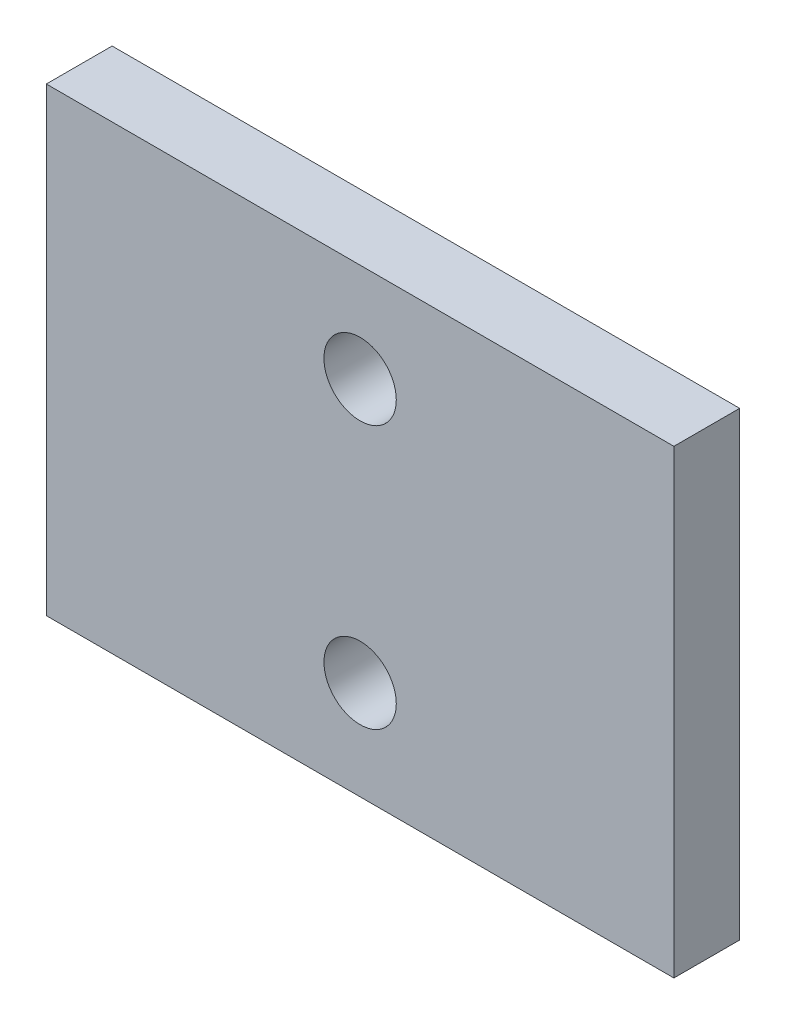
SolidWorks part; units mm, degrees
ref_plane "Front Plane" through (0, 0, 0) normal (0, 0, 1) x (1, 0, 0)
ref_plane "Top Plane" through (0, 0, 0) normal (0, 1, 0) x (1, 0, 0)
ref_plane "Right Plane" through (0, 0, 0) normal (1, 0, 0) x (0, 0, -1)
sketch "Sketch1" plane through (0, 0, 0) normal (0, 0, 1) x (1, 0, 0)
  line L0 (0, 0) -> (0, 40) construction
  line L2 (12.5, -15) -> (-12.5, -15)
  line L3 (12.5, -15) -> (12.5, 55)
  line L4 (12.5, 55) -> (-12.5, 55)
  line L5 (-12.5, -15) -> (-12.5, 55)
  line L6 (12.5, -15) -> (-12.5, 55) construction
  line L7 (12.5, 55) -> (-12.5, -15) construction
  circle A0 centre (0, 40) radius 7.9375
  circle A1 centre (0, 0) radius 7.9375
  point P5 (0, 20)
  dimension "D2" = 15.875
  dimension "D1" = 40
  dimension "D3" = 70
  dimension "D4" = 25
extrude "Boss-Extrude1" add sketch "Sketch1" along normal blind 10
sketch "Sketch2" plane through (0, 0, 10) normal (0, 0, 1) x (1, 0, 0)
  line L0 (12.5, 55) -> (-12.5, 55) construction
  line L1 (-47.7, 55) -> (-8.2, 55)
  line L3 (-47.7, -15) -> (-8.2, -15)
  line L4 (-8.2, 55) -> (-8.2, 35.0594)
  line L5 (-8.2, 35.0594) -> (-8.2, 32.231)
  line L6 (8.2, 35.0594) -> (8.2, 32.231)
  line L7 (-12.5, -15) -> (12.5, -15) construction
  line L8 (-8.2, 32.231) -> (-8.2, 4.0594)
  line L9 (-8.2, 1.231) -> (-8.2, 4.0594)
  line L16 (8.2, 1.231) -> (8.2, 4.0594)
  line L24 (8.2, 55) -> (8.2, 35.0594)
  line L25 (47.7, -15) -> (8.2, -15)
  line L27 (47.7, 55) -> (8.2, 55)
  line L28 (-47.7, 55) -> (-47.7, -15)
  line L29 (47.7, 55) -> (47.7, -15)
  line L31 (-8.2, 1.231) -> (-8.2, -15)
  line L32 (8.2, 1.231) -> (8.2, -15)
  line L33 (8.2, 32.231) -> (8.2, 4.0594)
extrude "Boss-Extrude2" add sketch "Sketch2" against normal up to surface (10 mm away) up to face at (0, 20, 0)
sketch "Sketch3" plane through (0, 0, 10) normal (0, 0, 1) x (1, 0, 0)
  circle A0 centre (0, 40) radius 5.5
  circle A1 centre (0, 0) radius 5.5
  circle A2 centre (0, 40) radius 7.9375 construction
  circle A3 centre (0, 40) radius 7.9375
  circle A4 centre (0, 0) radius 7.9375 construction
  circle A5 centre (0, 0) radius 7.9375
  dimension "D1" = 11
extrude "Boss-Extrude3" add sketch "Sketch3" against normal blind 8
